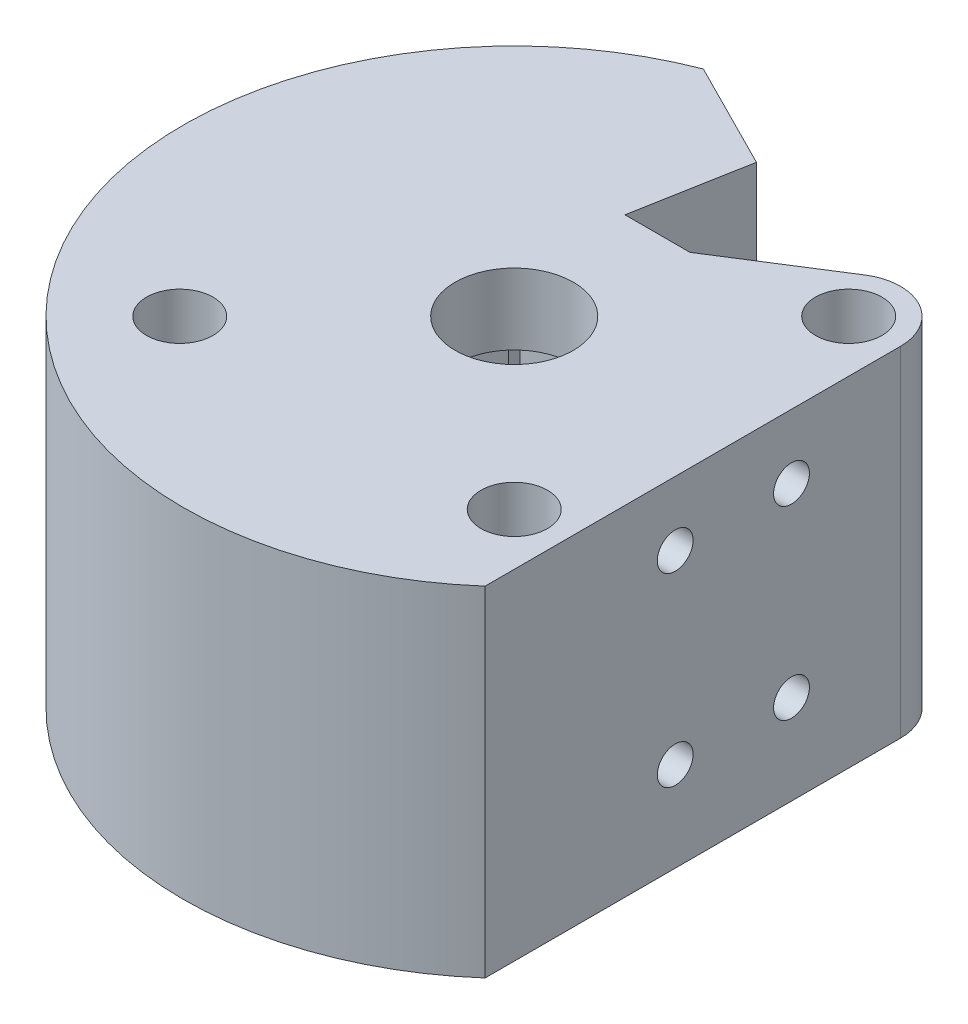
SolidWorks part; units mm, degrees
ref_plane "Front Plane" through (0, 0, 0) normal (0, 0, 1) x (1, 0, 0)
ref_plane "Top Plane" through (0, 0, 0) normal (0, 1, 0) x (1, 0, 0)
ref_plane "Right Plane" through (0, 0, 0) normal (1, 0, 0) x (0, 0, -1)
sketch "Sketch2" plane through (0, 0, 0) normal (0, 1, 0) x (1, 0, 0)
  line L0 (-46.3406, 15.0473) -> (-20.9548, -39.0545) construction
  line L1 (-17.9605, 17.9605) -> (-3.0236, 17.9605) construction
  line L2 (-17.9605, 17.9605) -> (-17.9605, -17.9605) construction
  line L3 (-17.9605, -17.9605) -> (17.9605, -17.9605) construction
  line L4 (17.9605, 17.9605) -> (17.9605, -17.9605) construction
  line L5 (-17.9605, 17.9605) -> (17.9605, -17.9605) construction
  line L6 (-17.9605, -17.9605) -> (17.9605, 17.9605) construction
  line L7 (10.05, -30.05) -> (-10.05, -30.05)
  line L8 (10.05, -30.05) -> (10.05, 10.05)
  line L9 (10.05, 10.05) -> (3.4925, 10.05)
  line L10 (-10.05, -30.05) -> (-10.05, 10.05)
  line L11 (10.05, -30.05) -> (-10.05, 10.05) construction
  line L12 (10.05, 10.05) -> (-10.05, -30.05) construction
  line L13 (-3.4925, 15.384) -> (3.4925, 15.384) construction
  line L14 (-3.4925, 15.384) -> (-3.4925, 10.05)
  line L15 (0, 10.05) -> (3.4925, 10.05) construction
  line L16 (3.4925, 15.384) -> (3.4925, 10.05)
  line L17 (0, 12.717) -> (3.4925, 10.05) construction
  line L18 (0, 12.717) -> (3.4925, 15.384) construction
  line L19 (-1.3182, 27.3309) -> (-10.8398, 32.142)
  line L20 (-1.3182, 27.3309) -> (-23.3118, -16.1961) construction
  line L21 (-23.3118, -16.1961) -> (-32.8333, -11.3851) construction
  line L22 (-10.8398, 32.142) -> (-32.8333, -11.3851) construction
  line L23 (-1.3182, 27.3309) -> (-32.8333, -11.3851) construction
  line L24 (-23.3118, -16.1961) -> (-10.8398, 32.142) construction
  line L25 (23.5324, -17.9605) -> (23.5324, -26.6597)
  line L26 (23.5324, -17.9605) -> (23.5324, 17.9605)
  line L27 (3.4925, 15.384) -> (14.9767, 22.6661)
  line L28 (-10.8398, 32.142) -> (-12.8493, 33.1573)
  line L29 (-3.4925, 15.384) -> (-1.3182, 27.3309)
  line L30 (-3.0236, 17.9605) -> (7.5558, 17.9605) construction
  line L31 (7.5558, 17.9605) -> (17.9605, 17.9605) construction
  line L32 (-3.4925, 15.384) -> (0, 12.717) construction
  line L33 (-3.4925, 10.05) -> (0, 12.717) construction
  line L34 (0, 10.05) -> (-3.4925, 10.05) construction
  line L35 (-3.4925, 10.05) -> (-10.05, 10.05)
  line L36 (-3.4925, 10.05) -> (0, 10.05) construction
  line L37 (3.4925, 10.05) -> (0, 10.05) construction
  arc A0 (-12.8493, 33.1573) -> (23.5324, -26.6597) centre (0, 0) ccw
  circle A1 centre (-17.9605, 17.9605) radius 3.5719 construction
  circle A2 centre (17.9605, 17.9605) radius 3.5719
  circle A3 centre (17.9605, -17.9605) radius 3.5719
  circle A4 centre (-17.9605, -17.9605) radius 3.5719
  arc A5 (-4.4901, 4.4901) -> (4.4901, 4.4901) centre (0, 0) ccw construction
  arc A6 (-7.1064, 7.1064) -> (7.1064, 7.1064) centre (0, 0) ccw construction
  circle A7 centre (-17.9605, -17.9605) radius 5.5719 construction
  arc A8 (23.5324, -17.9605) -> (17.9605, -12.3886) centre (17.9605, -17.9605) ccw construction
  arc A9 (23.5324, 17.9605) -> (14.9767, 22.6661) centre (17.9605, 17.9605) ccw
  arc A10 (23.5324, -26.6597) -> (-12.8493, 33.1573) centre (0, 0) ccw construction
  arc A11 (0, 10.05) -> (-7.1064, 7.1064) centre (0, 0) ccw construction
  arc A12 (4.4901, 4.4901) -> (-4.4901, 4.4901) centre (0, 0) ccw construction
  arc A13 (7.1064, 7.1064) -> (0, 10.05) centre (0, 0) ccw construction
  arc A14 (14.0206, 14.0206) -> (17.9605, 12.3886) centre (17.9605, 17.9605) ccw construction
  arc A15 (12.3886, 17.9605) -> (14.0206, 14.0206) centre (17.9605, 17.9605) ccw construction
  arc A16 (14.9767, 22.6661) -> (12.3886, 17.9605) centre (17.9605, 17.9605) ccw construction
  arc A17 (17.9605, 12.3886) -> (23.5324, 17.9605) centre (17.9605, 17.9605) ccw construction
  arc A18 (12.3886, -17.9605) -> (23.5324, -17.9605) centre (17.9605, -17.9605) ccw construction
  arc A19 (14.0206, -14.0206) -> (12.3886, -17.9605) centre (17.9605, -17.9605) ccw construction
  arc A20 (17.9605, -12.3886) -> (14.0206, -14.0206) centre (17.9605, -17.9605) ccw construction
  point P12 (0, -10)
  point P17 (0, 12.717)
  point P23 (-17.0758, 7.9729)
  point P35 (-32.1922, -15.1054)
  dimension "D1" = 71.12
  dimension "D3" = 7.1437
  dimension "D4" = 12.7
  dimension "D2" = 50.8
  dimension "D5" = 20.1
  dimension "D6" = 40.1
  dimension "D7" = 10
  dimension "D8" = 6.985
  dimension "D9" = 5.334
  dimension "D10" = 10.668
  dimension "D11" = 48.768
  dimension "D12" = 10.668
  dimension "D13" = 2
  dimension "D14" = 1
  dimension "D15" = 38.056
extrude "Boss-Extrude1" add sketch "Sketch2" along normal blind 1.905
sketch "Sketch3" plane through (0, 1.905, 0) normal (0, 1, 0) x (1, 0, 0)
  line L0 (-1.3182, 27.3309) -> (-23.3118, -16.1961) construction
  line L1 (-10.8398, 32.142) -> (-32.8333, -11.3851) construction
  line L2 (-23.3118, -16.1961) -> (-32.8333, -11.3851) construction
  line L3 (-10.8398, 32.142) -> (-32.8333, -11.3851)
  line L4 (-1.3182, 27.3309) -> (-9.7636, 10.6168)
  line L5 (-23.3118, -16.1961) -> (-32.8333, -11.3851)
  line L6 (-10.05, 10.05) -> (-9.415, 10.05) construction
  line L7 (-9.7636, 10.6168) -> (-10.05, 10.05) construction
  line L8 (-10.3364, 9.4832) -> (-23.3118, -16.1961)
  line L9 (-10.05, 10.05) -> (-10.3364, 9.4832) construction
  line L10 (-10.05, 9.415) -> (-10.05, 10.05) construction
  line L11 (-10.05, 10.05) -> (-3.4925, 10.05)
  line L12 (-3.4925, 10.05) -> (-3.4925, 15.384)
  line L13 (-3.4925, 15.384) -> (-1.3182, 27.3309)
  line L14 (-1.3182, 27.3309) -> (-12.8493, 33.1573)
  line L15 (23.5324, -26.6597) -> (23.5324, 17.9605)
  line L16 (14.9767, 22.6661) -> (3.4925, 15.384)
  line L17 (3.4925, 15.384) -> (3.4925, 10.05)
  line L18 (3.4925, 10.05) -> (10.05, 10.05)
  line L19 (10.05, 10.05) -> (10.05, -30.05)
  line L20 (10.05, -30.05) -> (-10.05, -30.05)
  line L21 (-10.05, -30.05) -> (-10.05, 10.05)
  line L22 (-9.415, 10.05) -> (-3.4925, 10.05)
  line L23 (-3.4925, 10.05) -> (-3.4925, 15.384)
  line L24 (-3.4925, 15.384) -> (-1.3182, 27.3309)
  line L25 (-10.8398, 32.142) -> (-12.8493, 33.1573)
  line L26 (23.5324, -26.6597) -> (23.5324, 17.9605)
  line L27 (14.9767, 22.6661) -> (3.4925, 15.384)
  line L28 (3.4925, 15.384) -> (3.4925, 10.05)
  line L29 (3.4925, 10.05) -> (10.05, 10.05)
  line L30 (10.05, 10.05) -> (10.05, -30.05)
  line L31 (10.05, -30.05) -> (-10.05, -30.05)
  line L32 (-10.05, -30.05) -> (-10.05, 9.415)
  line L33 (-1.3182, 27.3309) -> (-10.8398, 32.142) construction
  arc A0 (-10.3364, 9.4832) -> (-10.05, 9.415) centre (-10.05, 10.05) ccw
  circle A1 centre (17.9605, 17.9605) radius 3.5719 construction
  circle A2 centre (17.9605, -17.9605) radius 3.5719 construction
  arc A3 (-12.8493, 33.1573) -> (23.5324, -26.6597) centre (0, 0) ccw
  arc A4 (23.5324, 17.9605) -> (14.9767, 22.6661) centre (17.9605, 17.9605) ccw
  arc A5 (-12.8493, 33.1573) -> (23.5324, -26.6597) centre (0, 0) ccw
  arc A6 (23.5324, 17.9605) -> (14.9767, 22.6661) centre (17.9605, 17.9605) ccw
  circle A7 centre (-17.9605, -17.9605) radius 3.5719 construction
  circle A8 centre (17.9605, 17.9605) radius 3.5719
  circle A9 centre (17.9605, -17.9605) radius 3.5719
  circle A10 centre (-17.9605, -17.9605) radius 3.5719
  arc A11 (-9.7636, 10.6168) -> (-10.3364, 9.4832) centre (-10.05, 10.05) ccw construction
  arc A12 (-10.05, 9.415) -> (-9.415, 10.05) centre (-10.05, 10.05) ccw construction
  arc A13 (-9.415, 10.05) -> (-9.7636, 10.6168) centre (-10.05, 10.05) ccw
  dimension "D1" = 1.27
  dimension "D2" = 0
extrude "Boss-Extrude2" add sketch "Sketch3" along normal blind 19.558
sketch "Sketch4" plane through (0, 21.463, 0) normal (0, 1, 0) x (1, 0, 0)
  line L0 (0, 10.05) -> (3.4925, 10.05) construction
  line L1 (-3.4925, 15.384) -> (3.4925, 15.384) construction
  line L2 (0, 10.05) -> (-3.4925, 10.05) construction
  line L3 (0, 10.05) -> (-3.4925, 10.05)
  line L4 (0, 10.05) -> (3.4925, 10.05)
  line L5 (-3.4925, 15.384) -> (3.4925, 15.384)
  line L6 (-23.3118, -16.1961) -> (-32.8333, -11.3851) construction
  line L7 (-10.8398, 32.142) -> (-32.8333, -11.3851) construction
  line L8 (-1.3182, 27.3309) -> (-23.3118, -16.1961) construction
  line L9 (-23.3118, -16.1961) -> (-32.8333, -11.3851)
  line L10 (-10.8398, 32.142) -> (-32.8333, -11.3851)
  line L11 (-10.05, 10.05) -> (-3.4925, 10.05)
  line L12 (-10.05, -30.05) -> (-10.05, 10.05)
  line L13 (10.05, -30.05) -> (-10.05, -30.05)
  line L14 (10.05, 10.05) -> (10.05, -30.05)
  line L15 (3.4925, 10.05) -> (10.05, 10.05)
  line L16 (3.4925, 15.384) -> (3.4925, 10.05)
  line L17 (14.9767, 22.6661) -> (3.4925, 15.384)
  line L18 (23.5324, -26.6597) -> (23.5324, 17.9605)
  line L19 (-1.3182, 27.3309) -> (-12.8493, 33.1573)
  line L20 (-3.4925, 15.384) -> (-1.3182, 27.3309)
  line L21 (-3.4925, 10.05) -> (-3.4925, 15.384)
  line L22 (-9.415, 10.05) -> (-3.4925, 10.05)
  line L23 (-10.05, -30.05) -> (-10.05, 9.415)
  line L24 (10.05, -30.05) -> (-10.05, -30.05)
  line L25 (10.05, 10.05) -> (10.05, -30.05)
  line L26 (3.4925, 10.05) -> (10.05, 10.05)
  line L27 (3.4925, 15.384) -> (3.4925, 10.05) construction
  line L28 (14.9767, 22.6661) -> (3.4925, 15.384)
  line L29 (23.5324, -26.6597) -> (23.5324, 17.9605)
  line L30 (-10.8398, 32.142) -> (-12.8493, 33.1573)
  line L31 (-3.4925, 15.384) -> (-1.3182, 27.3309)
  line L32 (-3.4925, 10.05) -> (-3.4925, 15.384) construction
  line L33 (-1.3182, 27.3309) -> (-9.7636, 10.6168)
  line L34 (-1.3182, 27.3309) -> (-10.8398, 32.142) construction
  line L35 (-10.05, 10.05) -> (-10.3364, 9.4832) construction
  line L36 (-10.3364, 9.4832) -> (-23.3118, -16.1961)
  line L37 (-10.05, 9.415) -> (-10.05, 10.05) construction
  line L38 (-10.05, 10.05) -> (-9.415, 10.05) construction
  line L39 (-9.7636, 10.6168) -> (-10.05, 10.05) construction
  circle A0 centre (17.9605, 17.9605) radius 3.5719 construction
  circle A1 centre (17.9605, -17.9605) radius 3.5719 construction
  arc A2 (23.5324, 17.9605) -> (14.9767, 22.6661) centre (17.9605, 17.9605) ccw
  arc A3 (-12.8493, 33.1573) -> (23.5324, -26.6597) centre (0, 0) ccw
  arc A4 (23.5324, 17.9605) -> (14.9767, 22.6661) centre (17.9605, 17.9605) ccw
  arc A5 (-12.8493, 33.1573) -> (23.5324, -26.6597) centre (0, 0) ccw
  circle A6 centre (-17.9605, -17.9605) radius 3.5719 construction
  circle A7 centre (17.9605, 17.9605) radius 3.5719
  circle A8 centre (17.9605, -17.9605) radius 3.5719
  circle A9 centre (-17.9605, -17.9605) radius 3.5719
  arc A10 (-9.415, 10.05) -> (-9.7636, 10.6168) centre (-10.05, 10.05) ccw construction
  arc A11 (-10.3364, 9.4832) -> (-10.05, 9.415) centre (-10.05, 10.05) ccw construction
  arc A12 (-9.415, 10.05) -> (-9.7636, 10.6168) centre (-10.05, 10.05) ccw
  arc A13 (-10.3364, 9.4832) -> (-10.05, 9.415) centre (-10.05, 10.05) ccw
  dimension "D1" = 0
extrude "Boss-Extrude3" add sketch "Sketch4" along normal blind 7.366
sketch "Sketch5" plane through (0, 28.829, 0) normal (0, 1, 0) x (1, 0, 0)
  line L0 (3.4925, 15.384) -> (-3.4925, 15.384) construction
  line L1 (3.4925, 15.384) -> (-3.4925, 15.384)
  line L11 (-10.05, 10.05) -> (-3.4925, 10.05)
  line L12 (-10.05, -30.05) -> (-10.05, 10.05)
  line L13 (10.05, -30.05) -> (-10.05, -30.05)
  line L14 (10.05, 10.05) -> (10.05, -30.05)
  line L15 (3.4925, 10.05) -> (10.05, 10.05)
  line L16 (3.4925, 15.384) -> (3.4925, 10.05)
  line L17 (14.9767, 22.6661) -> (3.4925, 15.384)
  line L18 (23.5324, -26.6597) -> (23.5324, 17.9605)
  line L19 (-1.3182, 27.3309) -> (-12.8493, 33.1573)
  line L20 (-3.4925, 15.384) -> (-1.3182, 27.3309)
  line L21 (-3.4925, 10.05) -> (-3.4925, 15.384)
  line L22 (-10.05, 10.05) -> (-3.4925, 10.05) construction
  line L23 (-10.05, -30.05) -> (-10.05, 10.05) construction
  line L24 (10.05, -30.05) -> (-10.05, -30.05) construction
  line L25 (10.05, 10.05) -> (10.05, -30.05) construction
  line L26 (3.4925, 10.05) -> (10.05, 10.05) construction
  line L27 (3.4925, 15.384) -> (3.4925, 10.05) construction
  line L28 (14.9767, 22.6661) -> (3.4925, 15.384)
  line L29 (23.5324, -26.6597) -> (23.5324, 17.9605)
  line L30 (-1.3182, 27.3309) -> (-12.8493, 33.1573)
  line L31 (-3.4925, 15.384) -> (-1.3182, 27.3309)
  line L32 (-3.4925, 10.05) -> (-3.4925, 15.384) construction
  circle A0 centre (17.9605, 17.9605) radius 3.5719 construction
  circle A1 centre (17.9605, -17.9605) radius 3.5719 construction
  arc A2 (23.5324, 17.9605) -> (14.9767, 22.6661) centre (17.9605, 17.9605) ccw
  arc A3 (-12.8493, 33.1573) -> (23.5324, -26.6597) centre (0, 0) ccw
  arc A4 (23.5324, 17.9605) -> (14.9767, 22.6661) centre (17.9605, 17.9605) ccw
  arc A5 (-12.8493, 33.1573) -> (23.5324, -26.6597) centre (0, 0) ccw
  circle A6 centre (-17.9605, -17.9605) radius 3.5719 construction
  circle A7 centre (17.9605, 17.9605) radius 3.5719
  circle A8 centre (17.9605, -17.9605) radius 3.5719
  circle A9 centre (-17.9605, -17.9605) radius 3.5719
  arc A10 (4.4901, 4.4901) -> (-4.4901, 4.4901) centre (0, 0) ccw construction
  arc A11 (-4.4901, 4.4901) -> (4.4901, 4.4901) centre (0, 0) ccw construction
  arc A12 (4.4901, 4.4901) -> (-4.4901, 4.4901) centre (0, 0) ccw
  arc A13 (-4.4901, 4.4901) -> (4.4901, 4.4901) centre (0, 0) ccw
  dimension "D1" = 0
extrude "Boss-Extrude4" add sketch "Sketch5" along normal blind 7.62
sketch "Sketch6" plane through (23.5324, 0, 0) normal (1, 0, 0) x (0, 0, -1)
  line L1 (-6.243, 29.5506) -> (6.243, 29.5506) construction
  line L2 (-6.243, 29.5506) -> (-6.243, 9.6351) construction
  line L3 (-6.243, 9.6351) -> (6.243, 9.6351) construction
  line L4 (6.243, 29.5506) -> (6.243, 9.6351) construction
  line L5 (-6.243, 29.5506) -> (6.243, 9.6351) construction
  line L6 (-6.243, 9.6351) -> (6.243, 29.5506) construction
  circle A0 centre (-6.243, 29.5506) radius 1.925
  circle A1 centre (6.243, 29.5506) radius 1.925
  circle A2 centre (6.243, 9.6351) radius 1.925
  circle A3 centre (-6.243, 9.6351) radius 1.925
  point P0 (0, 19.5928)
  dimension "D3" = 3.85
  dimension "D1" = 19.9155
  dimension "D2" = 12.486
extrude "Cut-Extrude1" cut sketch "Sketch6" against normal blind 5.75
equation "\"AIRFRAME_OD\"= 3.142in"
equation "\"AIRFRAME_ID\"= 3.00in"
equation "\"FLAT_T\"= 0.125in"
equation "\"NOSE_EXP_L\"= 3.5in"
equation "\"NOSE_SHOULDER_L\"= 1.5in"
equation "\"MAIN_L\"= 30in"
equation "\"RECO_COUP_L\"= 6in"
equation "\"RECO_SWITCH_L\"= 1.5in"
equation "\"DROGUE_L\"= 14in"
equation "\"ATS_FORE_COUP_L\"= 4in"
equation "\"ATS_AFT_COUP_L\"= 2.5in"
equation "\"LOWER_L\"= 16in"
equation "\"FIN_N\"= 4"
equation "\"CR_AFT_X\"= 0.5in"
equation "\"CR_FORE_X\"= 6in"
equation "\"COUPLER_OD\"= 2.998in"
equation "\"COUPLER_ID\"= 2.875in"
equation "\"RECO_ROD_X\"= 1.5in"
equation "\"ATS_ROD_X\"= 2in"
equation "\"FIN_ROOT\"= 5in"
equation "\"FIN_X\"= 0.75in"
equation "\"MOTOR_OD\"= 2.25in"
equation "\"MOTOR_ID\"= 2.126in"
equation "\"MOTOR_L\"= 8in"
equation "\"MOTOR_LOWER_X\"= 0.5in"
equation "\"NOSE_CONE_L\"=14.5in"
equation "\"ATS_LIPO_L\" = 1.92in"
equation "\"ATS_LIPO_W\" = 0.42in"
equation "\"ATS_LIPO_H\" = 0.94in "
equation "\"ATS_STANDOFF_H\" = 10mm"
equation "\"ATS_STANDOFF_OD\" = 5.2mm"
equation "\"ATS_PCB_L\" = 2.5in"
equation "\"ATS_PCB_W\" = 1.45in"
equation "\"ATS_PCB_H\" = 1.2in"
equation "\"ATS_PCB_HOLESEP_W\" = 1.33in - 0.0985in"
equation "\"ATS_ALTI_L\" = 1.05in"
equation "\"ATS_ALTI_W\" = 0.7in"
equation "\"ATS_ALTI_H\" = 0.4in"
equation "\"D11@Sketch2\"=\"ATS_LIPO_L\""
equation "\"D12@Sketch2\"=\"ATS_LIPO_W\""
equation "\"D1@Boss-Extrude2\"=\"ATS_LIPO_H\""
